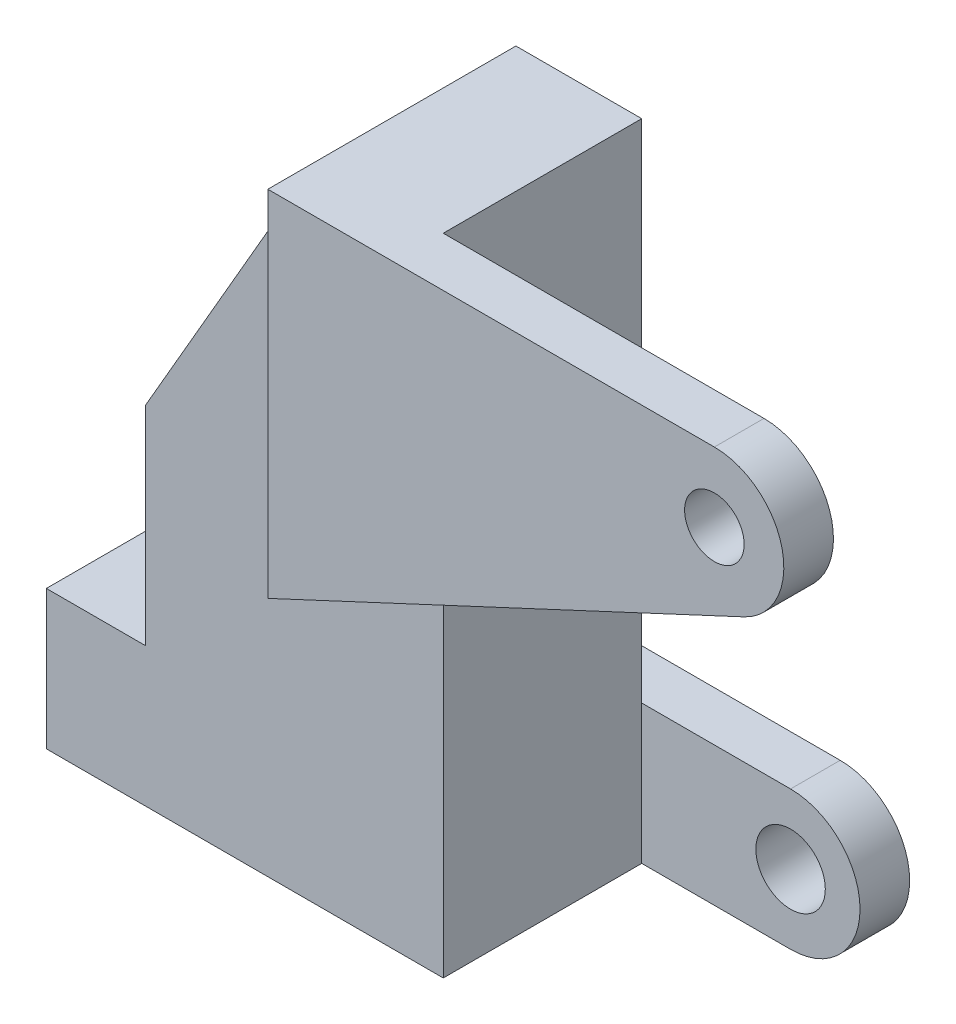
SolidWorks part; units mm, degrees
ref_plane "Front Plane" through (0, 0, 0) normal (0, 0, 1) x (1, 0, 0)
ref_plane "Top Plane" through (0, 0, 0) normal (0, 1, 0) x (1, 0, 0)
ref_plane "Right Plane" through (0, 0, 0) normal (1, 0, 0) x (0, 0, -1)
sketch "Sketch1" plane through (0, 0, 0) normal (0, 0, 1) x (1, 0, 0)
  line L0 (0, 0) -> (40, 0)
  line L1 (40, 0) -> (55, 0)
  line L2 (0, 0) -> (0, 9.9275)
  line L3 (0, 14) -> (0, 9.9275)
  line L4 (10, 14) -> (10, 35)
  line L5 (10, 35) -> (10, 54.8551)
  line L6 (10, 35) -> (27.3205, 65)
  line L7 (27.3205, 65) -> (72.3205, 65)
  line L8 (72.3205, 65) -> (72.3205, 58)
  line L9 (55, 0) -> (55, 7)
  line L10 (10, 14) -> (0, 14)
  line L11 (0, 14) -> (0, 0)
  line L12 (27.3205, 65) -> (27.3205, 29.2925)
  line L13 (27.3205, 29.2925) -> (75.2788, 51.6558)
  line L14 (27.3205, 65) -> (27.3205, 86.4638) construction
  line L15 (40, 0) -> (40, 14)
  line L16 (40, 14) -> (55, 14)
  line L17 (40, 14) -> (40, 35.2051)
  line L18 (40, 35.2051) -> (40, 65)
  line L19 (10, 14) -> (40, 14)
  line L20 (10, 14) -> (10, 0)
  circle A0 centre (72.3205, 58) radius 7
  circle A1 centre (55, 7) radius 7
  circle A2 centre (55, 7) radius 3.5
  circle A3 centre (72.3205, 58) radius 3
  dimension "D4" = 10
  dimension "D7" = 14
  dimension "D8" = 14
  dimension "D9" = 7
  dimension "D11" = 6
  dimension "D1" = 14
  dimension "D2" = 35
  dimension "D3" = 30
  dimension "D5" = 65
  dimension "D6" = 65
  dimension "D10" = 45
  dimension "D12" = 40
  dimension "D13" = 15
extrude "Boss-Extrude5" add sketch "Sketch1" along normal blind 20 contours L20 L10 L3 L2 L0 | L19 L20 L0 L15 | L4 L19 L17 L13 L12 L6 | L13 L18 L7 L12 region at (5, 7, 0) region at (25, 7, 0) region at (23.6899, 30.3792, 0) region at (33.4695, 48.5799, 0)
extrude "Boss-Extrude6" add sketch "Sketch1<4>" along normal blind 25 contours A0 L7 L18 L13 | A3 A0 | L13 L18 L7 L12 region at (52.5615, 52.8971, 0) region at (33.4695, 48.5799, 0) region at (65.6797, 56.5278, 0)
sketch "Sketch1<4>" plane through (0, 0, 0) normal (0, 0, 1) x (1, 0, 0) same geometry as "Sketch1"
extrude "Boss-Extrude7" add sketch "Sketch1<5>" against normal blind 5 contours L19 L20 L0 L15 | A1 L16 L15 L1 | A2 A1 region at (25, 7, 0) region at (44.8796, 7, 0) region at (48.198, 7, 0)
sketch "Sketch1<5>" plane through (0, 0, 0) normal (0, 0, 1) x (1, 0, 0) same geometry as "Sketch1"
extrude "Cut-Extrude1" cut sketch "Sketch1<6>" along normal blind 20 contours A0 L7 L18 L13 | A3 A0 region at (52.5615, 52.8971, 0) region at (65.6797, 56.5278, 0)
sketch "Sketch1<6>" plane through (0, 0, 0) normal (0, 0, 1) x (1, 0, 0) same geometry as "Sketch1"
